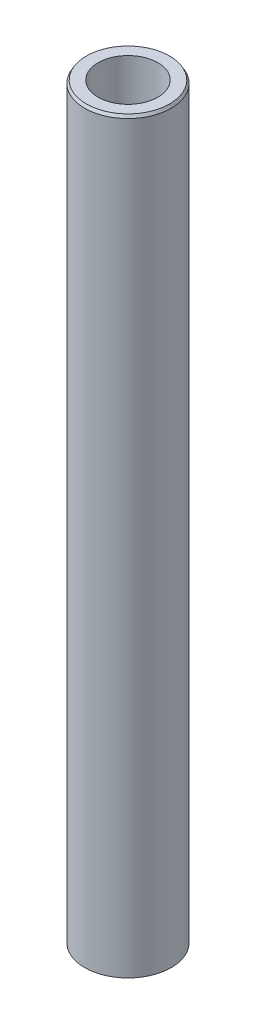
SolidWorks part; units mm, degrees
ref_plane "Front Plane" through (0, 0, 0) normal (0, 0, 1) x (1, 0, 0)
ref_plane "Top Plane" through (0, 0, 0) normal (0, 1, 0) x (1, 0, 0)
ref_plane "Right Plane" through (0, 0, 0) normal (1, 0, 0) x (0, 0, -1)
sketch "Sketch1" plane through (0, 0, 0) normal (0, 1, 0) x (1, 0, 0)
  circle A0 centre (0, 0) radius 25
  dimension "SHAFT_OD" = 50
extrude "Boss-Extrude1" add sketch "Sketch1" along normal blind 432.7697
sketch "Sketch2" plane through (0, 0, 0) normal (0, 1, 0) x (1, 0, 0)
  circle A0 centre (0, 0) radius 17.2777
  dimension "BORE_D" = 34.5555
extrude "Cut-Extrude1" cut sketch "Sketch2" along normal through all
chamfer "Chamfer1" distance 1.6632 angle 30 2 edges at (0, 432.7697, 25) (0, 0, 25) first distance on face at (0, 432.7697, 25) first distance on face at (0, 0, 17.2777)
